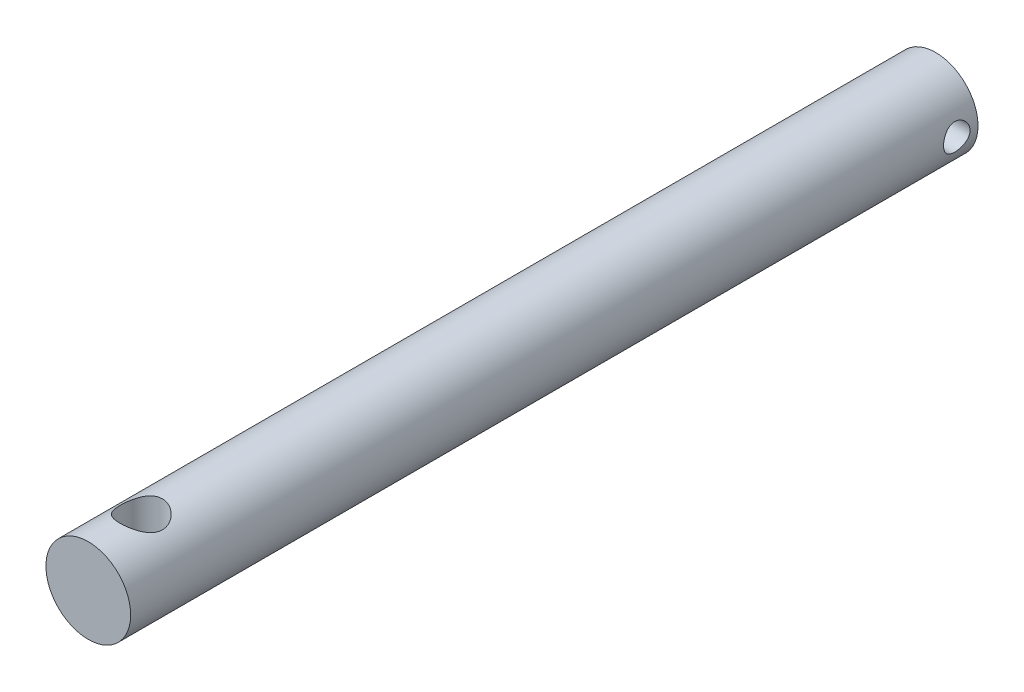
SolidWorks part; units mm, degrees
material "普通碳钢"
ref_plane "前视基准面" through (0, 0, 0) normal (0, 0, 1) x (1, 0, 0)
ref_plane "上视基准面" through (0, 0, 0) normal (0, 1, 0) x (1, 0, 0)
ref_plane "右视基准面" through (0, 0, 0) normal (1, 0, 0) x (0, 0, -1)
sketch "草图1" plane through (0, 0, 0) normal (0, 0, 1) x (1, 0, 0)
  circle A0 centre (0, 0) radius 8
  dimension "D1" = 16
extrude "凸台-拉伸1" add sketch "草图1" along normal blind 160
sketch "草图2" plane through (0, 0, 0) normal (0, 1, 0) x (1, 0, 0)
  line L0 (0, -136.9825) -> (0, -79.026) construction
  line L1 (-8, -160) -> (8, -160) construction
  circle A0 centre (0, -150) radius 4
  dimension "D1" = 8
  dimension "D2" = 10
extrude "切除-拉伸1" cut sketch "草图2" against normal blind 120 and the other way blind 120
sketch "草图3" plane through (0, 0, 0) normal (1, 0, 0) x (0, 0, -1)
  line L0 (0, 0) -> (-10.5111, 0) construction
  circle A0 centre (-4, 0) radius 2.5
  dimension "D1" = 5
  dimension "D2" = 4
extrude "切除-拉伸2" cut sketch "草图3" along normal blind 10
